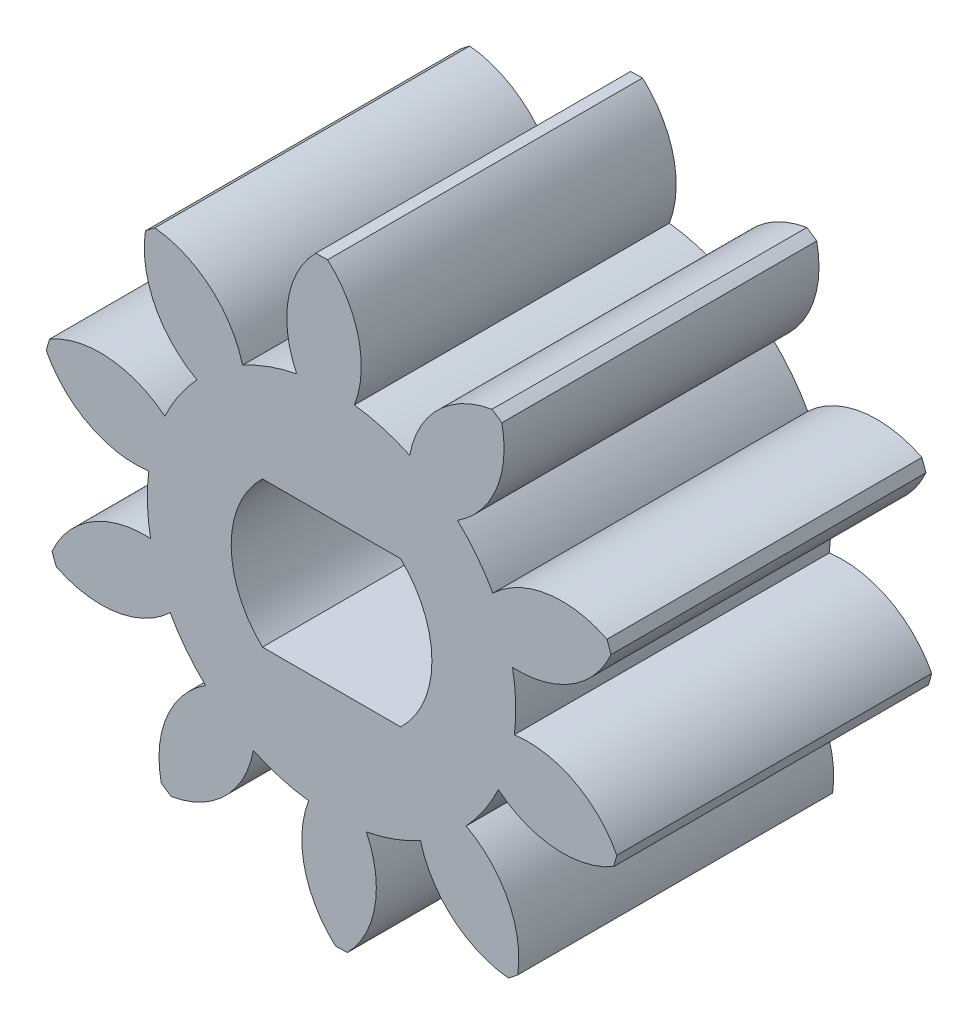
SolidWorks part; units mm, degrees
ref_plane "Ebene vorne" through (0, 0, 0) normal (0, 0, 1) x (1, 0, 0)
ref_plane "Ebene oben" through (0, 0, 0) normal (0, 1, 0) x (1, 0, 0)
ref_plane "Ebene rechts" through (0, 0, 0) normal (1, 0, 0) x (0, 0, -1)
sketch "Skizze1" plane through (0, 0, 0) normal (0, 0, 1) x (1, 0, 0)
  circle A0 centre (0, 0) radius 7.5
  dimension "D1" = 15
extrude "Aufsatz-Linear austragen1" add sketch "Skizze1" along normal blind 8
sketch "Skizze3" plane through (0, 0, 8) normal (0, 0, 1) x (1, 0, 0)
  circle A0 centre (0, 0) radius 7.5 construction
  arc A1 (1.9855, 4.2392) -> (0.5814, 4.6449) centre (0, 0) ccw
  arc A2 (-0.1001, 7.4993) -> (0.5814, 4.6449) centre (-1.8307, 5.5776) cw
  arc A3 (1.9855, 4.2392) -> (4.0742, 6.2969) centre (4.4916, 3.7842) cw
  arc A4 (4.0742, 6.2969) -> (-0.1001, 7.4993) centre (0, 0) ccw
extrude "Schnitt-Linear austragen1" cut sketch "Skizze3" against normal through all
pattern_circular "Kreismuster1" count 10 over 360 about axis through (0, 0, 8) along (0, 0, -1) of "Schnitt-Linear austragen1" reverse direction yes
sketch "Skizze4" plane through (0, 0, 8) normal (0, 0, 1) x (1, 0, 0)
  line L6 (1.755, -1.85) -> (-1.755, -1.85)
  line L8 (1.755, 1.85) -> (-1.755, 1.85)
  line L10 (2.228, -1.2404) -> (-2.228, 1.2404) construction
  line L11 (2.228, 1.2404) -> (-2.228, -1.2404) construction
  arc A4 (-1.755, 1.85) -> (-1.755, -1.85) centre (0, 0) ccw
  arc A5 (1.755, -1.85) -> (1.755, 1.85) centre (0, 0) ccw
extrude "Schnitt-Linear austragen3" cut sketch "Skizze4" against normal up to next
ref_axis "Achse1" through (0, 0, 0) along (0, 0, 1)
